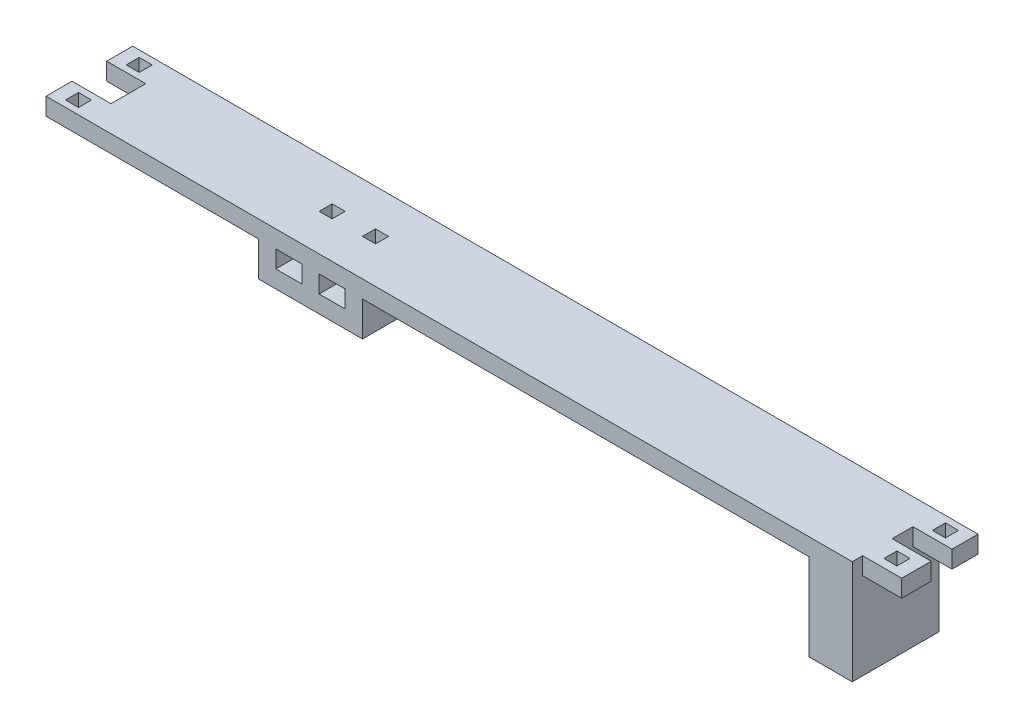
SolidWorks part; units mm, degrees
ref_plane "Front Plane" through (0, 0, 0) normal (0, 0, 1) x (1, 0, 0)
ref_plane "Top Plane" through (0, 0, 0) normal (0, 1, 0) x (1, 0, 0)
ref_plane "Right Plane" through (0, 0, 0) normal (1, 0, 0) x (0, 0, -1)
sketch "Sketch2" plane through (0, 0, 0) normal (0, 1, 0) x (1, 0, 0)
  line L1 (0, 0) -> (194.96, 0)
  line L2 (0, 0) -> (0, 6)
  line L3 (0, 6) -> (194.96, 6)
  line L4 (194.96, 0) -> (194.96, 6)
  dimension "D1" = 194.96
  dimension "D2" = 6
extrude "Boss-Extrude1" add sketch "Sketch2" along normal blind 4
sketch "Sketch3" plane through (0, 0, 0) normal (0, 0, -1) x (-1, 0, 0)
  line L0 (-194.96, 4) -> (0, 4) construction
  line L1 (-9, 4) -> (-185.96, 4)
  line L2 (-9, 4) -> (-9, 0)
  line L3 (-9, 0) -> (-185.96, 0)
  line L4 (-185.96, 4) -> (-185.96, 0)
  line L5 (-194.96, 0) -> (0, 0) construction
  line L7 (-194.96, 4) -> (-194.96, 0) construction
  line L8 (0, 4) -> (0, 0) construction
  dimension "D1" = 9
  dimension "D2" = 9
extrude "Boss-Extrude2" add sketch "Sketch3" against normal blind 14
sketch "Sketch4" plane through (9, 0, 0) normal (-1, 0, 0) x (0, 0, 1)
  line L0 (14, 0) -> (0, 0) construction
  line L1 (14, 4) -> (8, 4)
  line L2 (14, 4) -> (14, 0)
  line L3 (14, 0) -> (8, 0)
  line L4 (8, 4) -> (8, 0)
  line L6 (0, 0) -> (0, 4) construction
  dimension "D1" = 6
extrude "Boss-Extrude3" add sketch "Sketch4" along normal blind 9
sketch "Sketch5" plane through (185.96, 0, 0) normal (1, 0, 0) x (0, 0, -1)
  line L0 (-14, 4) -> (0, 4) construction
  line L1 (-11.6, 4) -> (-4.8, 4)
  line L2 (-11.6, 4) -> (-11.6, 0)
  line L3 (-11.6, 0) -> (-4.8, 0)
  line L4 (-4.8, 4) -> (-4.8, 0)
  line L5 (-14, 0) -> (0, 0) construction
  line L6 (-14, 4) -> (-14, 0) construction
  line L7 (0, 4) -> (0, 0) construction
  dimension "D1" = 2.4
  dimension "D2" = 4.8
extrude "Boss-Extrude4" add sketch "Sketch5" along normal blind 9
sketch "Sketch6" plane through (0, 4, 0) normal (0, 1, 0) x (1, 0, 0)
  line L0 (0, 6) -> (0, 0) construction
  line L1 (3, 4.5) -> (6, 4.5)
  line L2 (3, 4.5) -> (3, 1.5)
  line L3 (3, 1.5) -> (6, 1.5)
  line L4 (6, 4.5) -> (6, 1.5)
  line L5 (194.96, 6) -> (0, 6) construction
  line L7 (0, -14) -> (185.96, -14) construction
  line L8 (3, -9.5) -> (6, -9.5)
  line L9 (3, -9.5) -> (3, -12.5)
  line L10 (3, -12.5) -> (6, -12.5)
  line L11 (6, -9.5) -> (6, -12.5)
  line L12 (0, -14) -> (0, -8) construction
  line L13 (194.96, 0) -> (194.96, 6) construction
  line L14 (188.96, 4.5) -> (191.96, 4.5)
  line L15 (188.96, 4.5) -> (188.96, 1.5)
  line L16 (188.96, 1.5) -> (191.96, 1.5)
  line L17 (191.96, 4.5) -> (191.96, 1.5)
  line L18 (194.96, -4.8) -> (194.96, -11.6) construction
  line L19 (191.96, -6.7) -> (188.96, -6.7)
  line L20 (191.96, -6.7) -> (191.96, -9.7)
  line L21 (191.96, -9.7) -> (188.96, -9.7)
  line L22 (188.96, -6.7) -> (188.96, -9.7)
  line L23 (194.96, -4.8) -> (185.96, -4.8) construction
  dimension "D1" = 3
  dimension "D2" = 3
  dimension "D3" = 3
  dimension "D4" = 1.5
  dimension "D5" = 3
  dimension "D6" = 1.5
  dimension "D7" = 3
  dimension "D8" = 1.5
  dimension "D9" = 3
  dimension "D10" = 3
  dimension "D11" = 3
  dimension "D12" = 3
  dimension "D13" = 3
  dimension "D14" = 3
  dimension "D15" = 1.9
extrude "Cut-Extrude1" cut sketch "Sketch6" against normal up to next
sketch "Sketch7" plane through (0, 0, 0) normal (0, -1, 0) x (1, 0, 0)
  line L0 (194.96, -6) -> (0, -6) construction
  line L1 (185.96, 14) -> (175.96, 14)
  line L2 (185.96, 14) -> (185.96, -6)
  line L3 (185.96, -6) -> (175.96, -6)
  line L4 (175.96, 14) -> (175.96, -6)
  dimension "D1" = 10
extrude "Boss-Extrude5" add sketch "Sketch7" along normal blind 20
sketch "Sketch8" plane through (0, 0, 0) normal (0, -1, 0) x (1, 0, 0)
  line L0 (175.96, -6) -> (0, -6) construction
  line L1 (49, -6) -> (185.96, -6)
  line L2 (49, -6) -> (49, 0)
  line L3 (49, 0) -> (185.96, 0)
  line L4 (185.96, -6) -> (185.96, 0)
  line L5 (185.96, -6) -> (185.96, 14) construction
  line L6 (9, 8) -> (9, 0) construction
  dimension "D1" = 40
  dimension "D2" = 6
extrude "Boss-Extrude6" add sketch "Sketch8" along normal blind 8
chamfer "Chamfer1" distance 12 angle 50 1 edges at (175.96, -8, -3) first distance on face at (175.96, -9.3333, 2.6667)
sketch "Sketch9" plane through (0, 0, 0) normal (0, 0, 1) x (1, 0, 0)
  line L0 (175.96, 0) -> (0, 0) construction
  line L1 (49, -8) -> (55, -8)
  line L2 (49, -8) -> (49, 0)
  line L3 (49, 0) -> (55, 0)
  line L5 (161.659, -8) -> (49, -8) construction
  line L6 (61, -8) -> (73, -8)
  line L8 (61, 0) -> (73, 0)
  line L9 (73, -8) -> (73, 0)
  line L10 (175.96, 0) -> (49, 0) construction
  line L11 (55, 0) -> (61, 0)
  line L12 (55, -8) -> (61, -8)
  dimension "D1" = 24
extrude "Boss-Extrude7" add sketch "Sketch9" along normal up to surface (14 mm away) up to face at (120.64, -5.3333, 14)
sketch "Sketch10" plane through (0, 0, 14) normal (0, 0, 1) x (1, 0, 0)
  line L0 (49, 0) -> (0, 0) construction
  line L1 (53, 0) -> (59, 0)
  line L2 (53, 0) -> (53, -4)
  line L3 (53, -4) -> (59, -4)
  line L4 (59, 0) -> (59, -4)
  line L5 (49, 0) -> (49, -8) construction
  line L7 (63, 0) -> (69, 0)
  line L8 (63, 0) -> (63, -4)
  line L9 (63, -4) -> (69, -4)
  line L10 (69, 0) -> (69, -4)
  dimension "D1" = 6
  dimension "D2" = 4
  dimension "D3" = 0
  dimension "D4" = 4
  dimension "D5" = 6
  dimension "D6" = 4
extrude "Cut-Extrude2" cut sketch "Sketch10" against normal up to next
sketch "Sketch11" plane through (0, 4, 0) normal (0, 1, 0) x (1, 0, 0)
  line L0 (53, 6) -> (53, -14) construction
  line L1 (54.5, -2.5) -> (57.5, -2.5)
  line L2 (54.5, -2.5) -> (54.5, -5.5)
  line L3 (54.5, -5.5) -> (57.5, -5.5)
  line L4 (57.5, -2.5) -> (57.5, -5.5)
  line L5 (0, -14) -> (185.96, -14) construction
  line L8 (63, 6) -> (63, -14) construction
  line L9 (64.5, -5.5) -> (67.5, -5.5)
  line L10 (64.5, -5.5) -> (64.5, -2.5)
  line L11 (64.5, -2.5) -> (67.5, -2.5)
  line L12 (67.5, -5.5) -> (67.5, -2.5)
  dimension "D1" = 1.5
  dimension "D2" = 3
  dimension "D3" = 3
  dimension "D4" = 8.5
  dimension "D5" = 3
  dimension "D6" = 3
  dimension "D7" = 1.5
  dimension "D8" = 8.5
extrude "Cut-Extrude3" cut sketch "Sketch11" against normal up to next
